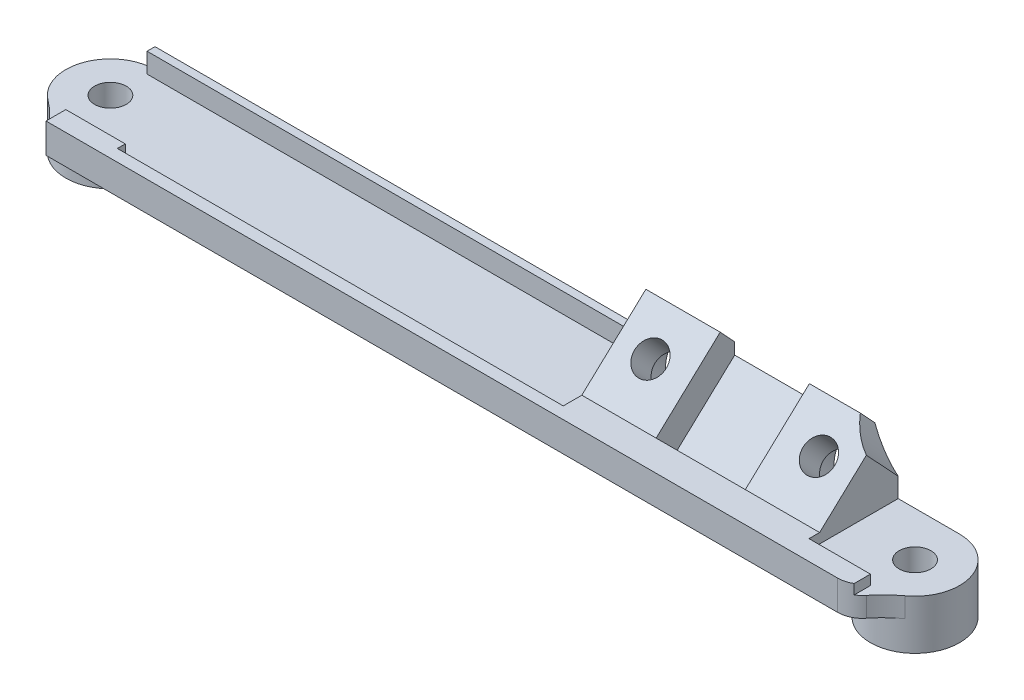
SolidWorks part; units mm, degrees
ref_plane "前视基准面" through (0, 0, 0) normal (0, 0, 1) x (1, 0, 0)
ref_plane "上视基准面" through (0, 0, 0) normal (0, 1, 0) x (1, 0, 0)
ref_plane "右视基准面" through (0, 0, 0) normal (1, 0, 0) x (0, 0, -1)
other "Configuration Table"
sketch "草图1" plane through (0, 0, 0) normal (0, 1, 0) x (1, 0, 0)
  circle A0 centre (0, 0) radius 1.6
  circle A1 centre (0, 0) radius 4.5
  dimension "D1" = 3.2
  dimension "D2" = 9
extrude "凸台-拉伸1" add sketch "草图1" along normal blind 3
sketch "草图2" plane through (0, 3, 0) normal (0, 1, 0) x (1, 0, 0)
  line L0 (0, 0) -> (81.2, 0) construction
  line L1 (0, 4.5) -> (81.2, 4.5)
  line L2 (0, -4.5) -> (81.2, -4.5)
  arc A0 (0, 4.5) -> (0, -4.5) centre (0, 0) ccw
  arc A1 (81.2, -4.5) -> (81.2, 4.5) centre (81.2, 0) ccw
  circle A2 centre (0, 0) radius 4.5 construction
  circle A3 centre (81.2, 0) radius 1.6
  circle A4 centre (0, 0) radius 1.6 construction
  circle A5 centre (0, 0) radius 1.6
  point P3 (40.6, 0)
  dimension "D1" = 81.2
extrude "凸台-拉伸2" add sketch "草图2" along normal blind 2
ref_plane "基准面1" through (75, 0, 0) normal (1, 0, 0) x (0, 0, -1)
sketch "草图3" plane through (75, 0, 0) normal (1, 0, 0) x (0, 0, -1)
  line L0 (-4.5, 5) -> (4.5, 13.3926)
  line L1 (4.5, 13.3926) -> (4.5, 5)
  line L2 (4.5, 5) -> (-4.5, 5)
  dimension "D1" = 43
extrude "凸台-拉伸3" add sketch "草图3" against normal blind 24
sketch "草图4" plane through (0, 4.9189, 4.587) normal (0, 0.7314, 0.682) x (1, 0, 0)
  line L0 (51, 6.2719) -> (75, 6.2719) construction
  line L1 (51, 12.4248) -> (51, 0.1189) construction
  line L2 (75, -4.95) -> (75, 4.95) construction
  line L3 (63, 12.4248) -> (63, 0.1189) construction
  line L4 (51, 12.4248) -> (75, 12.4248) construction
  line L5 (51, 0.1189) -> (75, 0.1189) construction
  circle A0 centre (54.5, 6.2719) radius 1.6
  circle A1 centre (71.5, 6.2719) radius 1.6
  dimension "D1" = 3.2
  dimension "D3" = 17
extrude "切除-拉伸1" cut sketch "草图4" against normal up to next
sketch "草图6" plane through (0, 4.9189, 4.587) normal (0, 0.7314, 0.682) x (1, 0, 0)
  line L0 (51, 12.4248) -> (75, 12.4248) construction
  line L1 (58.5, 12.4248) -> (67.5, 12.4248)
  line L2 (58.5, 12.4248) -> (58.5, -1.2451)
  line L3 (58.5, -1.2451) -> (67.5, -1.2451)
  line L4 (67.5, 12.4248) -> (67.5, -1.2451)
  line L5 (0, -1.2451) -> (81.2, -1.2451) construction
  circle A0 centre (54.5, 6.2719) radius 1.6 construction
  circle A1 centre (71.5, 6.2719) radius 1.6 construction
  dimension "D1" = 4
  dimension "D2" = 4
extrude "切除-拉伸2" cut sketch "草图6" against normal blind 3
ref_plane "基准面2" through (0, 2.7248, 2.541) normal (0, 0.7314, 0.682) x (1, 0, 0)
sketch "草图7" plane through (0, 2.7248, 2.541) normal (0, 0.7314, 0.682) x (1, 0, 0)
  circle A0 centre (54.5, 6.2719) radius 3
  circle A1 centre (71.5, 6.2719) radius 3
  dimension "D1" = 6
  dimension "D2" = 6
extrude "切除-拉伸3" cut sketch "草图7" against normal up to next
sketch "草图8" plane through (0, 3, 0) normal (0, -1, 0) x (1, 0, 0)
  circle A0 centre (81.2, 0) radius 4.5
  circle A1 centre (81.2, 0) radius 1.6 construction
  circle A2 centre (81.2, 0) radius 1.6
extrude "凸台-拉伸4" add sketch "草图8" along normal up to surface (3 mm away) up to face at (0, 0, 4.5)
sketch "草图9" plane through (0, 4.9189, 4.587) normal (0, 0.7314, 0.682) x (1, 0, 0)
  circle A0 centre (77.925, 13.2719) radius 6
  circle A1 centre (71.5, 6.2719) radius 1.6 construction
  dimension "D1" = 6.425
  dimension "D2" = 12
  dimension "D3" = 7
extrude "切除-拉伸4" cut sketch "草图9" against normal up to next
sketch "草图10" plane through (0, 5, 0) normal (0, 1, 0) x (1, 0, 0)
  line L0 (51, 4.5) -> (51, -4.5) construction
  line L1 (51, 3.7) -> (0, 3.7)
  line L2 (51, 3.7) -> (51, 4.5)
  line L3 (51, 4.5) -> (0, 4.5)
  line L4 (0, 3.7) -> (0, 4.5)
  line L5 (9, 4.5) -> (9, -4.5) construction
  line L6 (0, -4.5) -> (51, -4.5) construction
  line L7 (51, -4.5) -> (51, 4.5) construction
  dimension "D1" = 0.8
  dimension "D2" = 42
extrude "凸台-拉伸5" add sketch "草图10" along normal blind 2
sketch "草图11" plane through (0, 5, 0) normal (0, 1, 0) x (1, 0, 0)
  line L2 (0, -4.5) -> (81.2, -4.5)
  line L3 (0, -4.5) -> (0, -6.5)
  line L4 (0, -6.5) -> (81.2, -6.5)
  line L5 (81.2, -4.5) -> (81.2, -6.5)
  dimension "D1" = 2
extrude "凸台-拉伸6" add sketch "草图11" along normal blind 1 and the other way up to surface other way up to face at (55.5333, 3, 0.095)
fillet "圆角1" radius 10 2 edges at (81.2, 4, 4.5) (0, 4, 4.5)
sketch "草图12" plane through (0, 5, 0) normal (0, 1, 0) x (1, 0, 0)
  line L0 (0, 3.7) -> (51, 3.7) construction
  line L1 (51, -4.5) -> (6, -4.5)
  line L2 (51, -4.5) -> (51, -5.3)
  line L3 (51, -5.3) -> (6, -5.3)
  line L4 (6, -4.5) -> (6, -5.3)
  line L5 (51, -4.5) -> (51, 3.7) construction
  dimension "D1" = 9
  dimension "D2" = 45
extrude "切除-拉伸5" cut sketch "草图12" along normal up to next
sketch "草图13" plane through (75, 0, 0) normal (1, 0, 0) x (0, 0, -1)
  line L0 (-4.5, 6) -> (-3.4276, 6)
  line L1 (1.2881, 10.3975) -> (-4.5, 5) construction
  line L2 (-3.4276, 6) -> (-4.5, 5)
  line L3 (-3.6406, 5) -> (-6.5, 5) construction
  line L4 (-4.5, 5) -> (-4.5, 6) construction
  line L5 (-4.5, 5) -> (-4.5, 6)
extrude "凸台-拉伸7" add sketch "草图13" against normal up to surface (24 mm away) up to face at (51, 7.4785, -2.38)
sketch "草图14" plane through (58.5, 0, 0) normal (1, 0, 0) x (0, 0, -1)
  line L0 (-3.4276, 6) -> (-1.3816, 3.8059)
  line L1 (-1.3816, 3.8059) -> (-2.2459, 3)
  line L2 (-2.2459, 3) -> (-4.5, 3)
  line L3 (-4.5, 3) -> (-4.5, 5)
  line L4 (-4.5, 5) -> (-3.4276, 6)
  line L5 (4.5, 13.3926) -> (-3.4276, 6) construction
  line L6 (0.4759, 5.5381) -> (-5.5578, -0.0884) construction
extrude "凸台-拉伸8" add sketch "草图14" along normal up to surface (9 mm away) up to face at (67.5, 6.6139, 0.9456)
sketch "草图15" plane through (0, 4.9189, 4.587) normal (0, 0.7314, 0.682) x (1, 0, 0)
  line L1 (72.6435, 10.4248) -> (51, 10.4248)
  line L2 (72.6435, 10.4248) -> (72.6435, 12.4248)
  line L3 (72.6435, 12.4248) -> (51, 12.4248)
  line L4 (51, 10.4248) -> (51, 12.4248)
  arc A0 (71.9851, 12.4248) -> (75, 8.0331) centre (77.925, 13.2719) ccw construction
  dimension "D1" = 2
extrude "切除-拉伸6" cut sketch "草图15" against normal up to next
sketch "草图16" plane through (0, 6, 0) normal (0, 1, 0) x (1, 0, 0)
  line L0 (0, -6.5) -> (81.2, -6.5) construction
  line L1 (79.9002, -6.5) -> (81.2, -6.5)
  arc A0 (79.9002, -6.5) -> (81.8647, -5.5462) centre (79.9002, -4) ccw
  arc A1 (83.845, -3.6406) -> (81.2, -6.5) centre (89.7229, -11.7308) ccw construction
  arc A2 (81.8647, -5.5462) -> (81.2, -6.5) centre (89.7229, -11.7308) ccw
  dimension "D1" = 5
extrude "切除-拉伸7" cut sketch "草图16" against normal up to next
